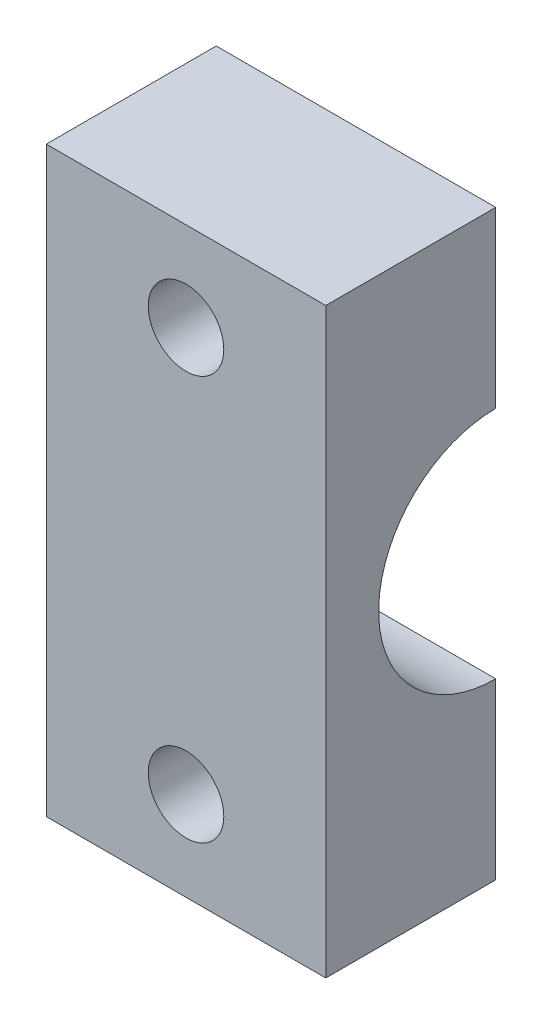
SolidWorks part; units mm, degrees
material "ABS"
ref_plane "Front Plane" through (0, 0, 0) normal (0, 0, 1) x (1, 0, 0)
ref_plane "Top Plane" through (0, 0, 0) normal (0, 1, 0) x (1, 0, 0)
ref_plane "Right Plane" through (0, 0, 0) normal (1, 0, 0) x (0, 0, -1)
sketch "Sketch2" plane through (0, 0, 0) normal (1, 0, 0) x (0, 0, -1)
  line L1 (-90, -4.5) -> (90, -4.5)
  line L2 (-90, -4.5) -> (-90, 4.5)
  line L3 (-90, 4.5) -> (90, 4.5)
  line L4 (90, -4.5) -> (90, 4.5)
  line L5 (-90, -4.5) -> (90, 4.5) construction
  line L6 (-90, 4.5) -> (90, -4.5) construction
  point P0 (0, 0)
  dimension "D1" = 9
  dimension "D2" = 180
extrude "Boss-Extrude1" add sketch "Sketch2" along normal blind 14.8
sketch "Sketch3" plane through (14.8, 0, 0) normal (1, 0, 0) x (0, 0, -1)
  line L0 (-90, -4.5) -> (90, -4.5) construction
  line L1 (-74.579, -4.5) -> (74.579, -4.5) construction
  line L7 (90, -4.5) -> (90, 4.5)
  line L8 (90, 4.5) -> (-90, 4.5)
  line L9 (-90, 4.5) -> (-90, -4.5)
  line L10 (-90, -4.5) -> (90, -4.5)
  line L11 (90, -4.5) -> (90, 4.5)
  line L12 (90, 4.5) -> (-90, 4.5)
  line L13 (-90, 4.5) -> (-90, -4.5)
  arc A0 (-68.379, -4.5) -> (-80.779, -4.5) centre (-74.579, -4.5) ccw
  arc A1 (80.779, -4.5) -> (68.379, -4.5) centre (74.579, -4.5) ccw
  point P10 (0, -4.5)
  dimension "D1" = 6.2
  dimension "D2" = 149.158
  dimension "D4" = 0
extrude "Bar Holes" [suppressed] cut sketch "Sketch3" against normal through all
sketch "Sketch6" [suppressed] plane through (0, 4.5, 0) normal (0, 1, 0) x (1, 0, 0)
  line L0 (7.4, 63.879) -> (7.4, -63.879) construction
  line L1 (14.8, 90) -> (0, 90) construction
  line L2 (14.8, -90) -> (0, -90) construction
  line L3 (0, -68.379) -> (14.8, -68.379) construction
  line L4 (0, -80.779) -> (14.8, -80.779) construction
  line L5 (-32.5661, 0) -> (77.6197, 0) construction
  circle A0 centre (7.4, 63.879) radius 2
  circle A1 centre (7.4, -63.879) radius 2
  circle A2 centre (7.4, -85.279) radius 2
  circle A3 centre (7.4, 85.279) radius 2
  circle A4 centre (7.4, -32.5) radius 3.5 construction
  circle A5 centre (7.4, 32.5) radius 3.5 construction
  point P4 (7.4, 0)
  point P8 (7.4, 90)
  point P17 (7.4, -90)
  dimension "D1" = 4
  dimension "D2" = 4
  dimension "D5" = 4
  dimension "D6" = 4
  dimension "D10" = 7
  dimension "D11" = 7
  dimension "D7" = 32.5
  dimension "D3" = 4.5
  dimension "D4" = 4.5
  dimension "D8" = 4.5
  dimension "D9" = 32.5
extrude "Bolt Holes" [suppressed] cut sketch "Sketch6" against normal through all
sketch "Sketch7" plane through (14.8, 0, 0) normal (1, 0, 0) x (0, 0, -1)
  line L0 (-90, -4.5) -> (90, -4.5) construction
  line L1 (-45, -4.5) -> (45, -4.5)
  line L2 (-45, -4.5) -> (-45, 0)
  line L3 (-45, 0) -> (45, 0)
  line L4 (45, -4.5) -> (45, 0)
  point P6 (0, 0)
  dimension "D1" = 90
extrude "Cut-Extrude1" cut sketch "Sketch7" against normal through all
fillet "Fillet1" radius 8 2 edges at (7.4, 0, -45) (7.4, 0, 45)
sketch "Sketch8" plane through (14.8, 0, 0) normal (1, 0, 0) x (0, 0, -1)
  line L0 (83.579, -39.5) -> (83.579, -54.92)
  line L1 (83.579, -4.5) -> (83.579, -39.5)
  line L2 (83.579, -39.5) -> (74.579, -39.5) construction
  line L3 (74.579, -33.3) -> (74.579, -4.5)
  line L4 (45, -4.5) -> (90, -4.5) construction
  line L5 (74.579, -4.5) -> (83.579, -4.5)
  line L6 (83.579, -54.92) -> (74.579, -54.92)
  line L7 (74.579, -54.92) -> (74.579, -45.7)
  line L8 (0, -7.0607) -> (0, -71.6637) construction
  line L9 (-74.579, -54.92) -> (-74.579, -45.7)
  line L10 (-83.579, -54.92) -> (-74.579, -54.92)
  line L11 (-83.579, -39.5) -> (-83.579, -54.92)
  line L12 (-83.579, -4.5) -> (-83.579, -39.5)
  line L13 (-74.579, -4.5) -> (-83.579, -4.5)
  line L14 (-74.579, -33.3) -> (-74.579, -4.5)
  arc A0 (74.579, -45.7) -> (74.579, -33.3) centre (74.579, -39.5) ccw
  arc A1 (-74.579, -45.7) -> (-74.579, -33.3) centre (-74.579, -39.5) cw
  dimension "D1" = 15.42
  dimension "D2" = 35
  dimension "D3" = 9
extrude "Boss-Extrude2" add sketch "Sketch8" against normal blind 14.8
sketch "Sketch11" plane through (0, 0, 74.579) normal (0, 0, -1) x (-1, 0, 0)
  line L0 (-7.4, -33.3) -> (-7.4, -28.8) construction
  line L1 (0, -33.3) -> (-14.8, -33.3) construction
  line L2 (-7.4, -33.3) -> (-7.4, -45.7) construction
  line L3 (0, -45.7) -> (-14.8, -45.7) construction
  line L4 (-7.4, -39.5) -> (0, -39.5) construction
  circle A1 centre (-7.4, -28.8) radius 2
  circle A2 centre (-7.4, -50.2) radius 2
  dimension "D1" = 4.5
extrude "Cut-Extrude2" cut sketch "Sketch11" along normal through all both and the other way through all
sketch "Sketch12" plane through (0, 0, 0) normal (-1, 0, 0) x (0, 0, 1)
  line L4 (96.9862, 8.7415) -> (-95.1532, 8.7415)
  line L5 (96.9862, 8.7415) -> (96.9862, -4.5)
  line L9 (-95.1532, 8.7415) -> (-95.1532, -16.0389)
  line L11 (96.9862, -16.0389) -> (96.9862, -4.5)
  line L12 (74.579, -33.3) -> (74.579, -24.08) construction
  line L13 (74.579, -33.3) -> (74.579, -4.5) construction
  line L15 (74.579, -24.08) -> (96.9862, -24.08)
  line L16 (96.9862, -24.08) -> (96.9862, -16.0389)
  line L17 (74.579, -24.08) -> (-68.9561, -24.08)
  line L18 (-95.1532, -24.08) -> (-95.1532, -16.0389)
  line L20 (-95.1532, -24.08) -> (-95.1532, -55.6267)
  line L21 (-95.1532, -55.6267) -> (-68.9561, -55.6267)
  line L22 (-68.9561, -24.08) -> (-68.9561, -55.6267)
  dimension "D1" = 9.22
extrude "Cut-Extrude3" cut sketch "Sketch12" against normal through all both
